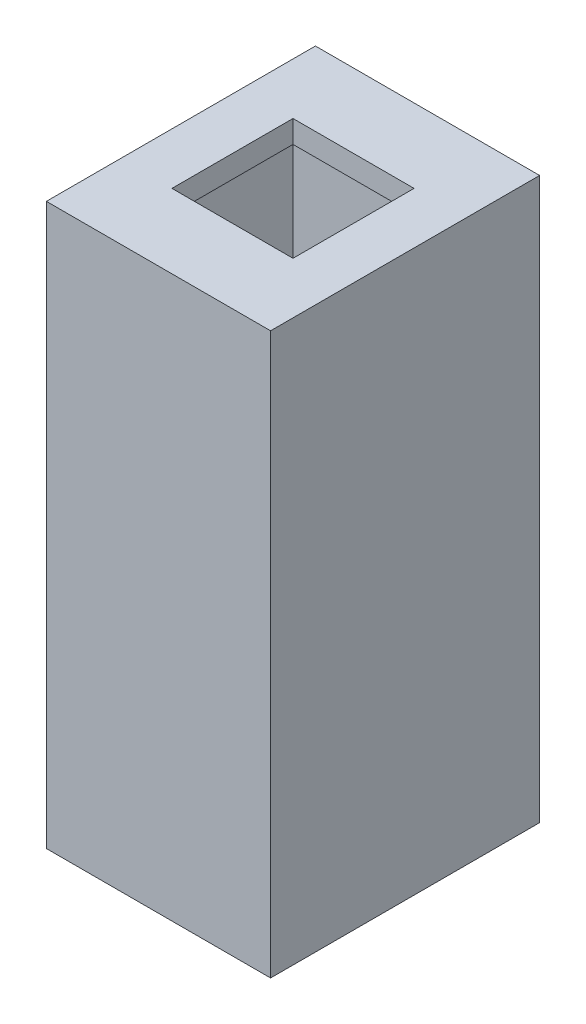
SolidWorks part; units mm, degrees
ref_plane "前视基准面" through (0, 0, 0) normal (0, 0, 1) x (1, 0, 0)
ref_plane "上视基准面" through (0, 0, 0) normal (0, 1, 0) x (1, 0, 0)
ref_plane "右视基准面" through (0, 0, 0) normal (1, 0, 0) x (0, 0, -1)
other "Configuration Table"
sketch "草图1" plane through (0, 0, 0) normal (0, 1, 0) x (1, 0, 0)
  line L1 (-3.1, 3.1) -> (3.1, 3.1)
  line L2 (-3.1, 3.1) -> (-3.1, -3.1)
  line L3 (-3.1, -3.1) -> (3.1, -3.1)
  line L4 (3.1, 3.1) -> (3.1, -3.1)
  line L5 (-3.1, 3.1) -> (3.1, -3.1) construction
  line L6 (-3.1, -3.1) -> (3.1, 3.1) construction
  line L7 (-5, 6) -> (5, 6)
  line L8 (-5, 6) -> (-5, -6)
  line L9 (-5, -6) -> (5, -6)
  line L10 (5, 6) -> (5, -6)
  line L11 (-5, 6) -> (5, -6) construction
  line L12 (-5, -6) -> (5, 6) construction
  line L13 (-2.7, -2.7) -> (2.7, -2.7)
  line L14 (-2.7, -2.7) -> (-2.7, 2.7)
  line L15 (-2.7, 2.7) -> (2.7, 2.7)
  line L16 (2.7, -2.7) -> (2.7, 2.7)
  line L17 (-2.7, -2.7) -> (2.7, 2.7) construction
  line L18 (-2.7, 2.7) -> (2.7, -2.7) construction
  point P0 (0, 0)
  point P5 (0, 0)
  point P13 (0, 0)
  dimension "D1" = 6.2
  dimension "D2" = 12
  dimension "D3" = 5.4
  dimension "D4" = 10
extrude "凸台-拉伸1" add sketch "草图1" along normal blind 25 contours L10 L7 L8 L9 L1 L4 L3 L2 region at (0, 0, -5.8438)
extrude "凸台-拉伸2" add sketch "草图1<3>" against normal blind 1 from surface contours L10 L7 L8 L9 L1 L4 L3 L2 | L4 L1 L2 L3 L16 L13 L14 L15 region at (0, 0, -3.0123) region at (0, 0, -5.8438) starting at face at (0, 25, 0)
sketch "草图1<3>" plane through (0, 0, 0) normal (0, 1, 0) x (1, 0, 0) same geometry as "草图1"
sketch "草图2" plane through (0, 0, 0) normal (0, -1, 0) x (1, 0, 0)
  line L1 (-3, -3) -> (3, -3)
  line L2 (-3, -3) -> (-3, 3)
  line L3 (-3, 3) -> (3, 3)
  line L4 (3, -3) -> (3, 3)
  line L5 (-3, -3) -> (3, 3) construction
  line L6 (-3, 3) -> (3, -3) construction
  circle A0 centre (-3.75, 4.5) radius 0.3
  circle A1 centre (3.75, -4.5) radius 0.3
  circle A2 centre (3.75, 4.5) radius 0.3
  circle A3 centre (-3.75, -4.5) radius 0.3
  point P0 (0, 0)
  dimension "D2" = 0.6
  dimension "D1" = 6
extrude "切除-拉伸1" cut sketch "草图2" against normal blind 2 contours A0 | A2 | A3 | A1
